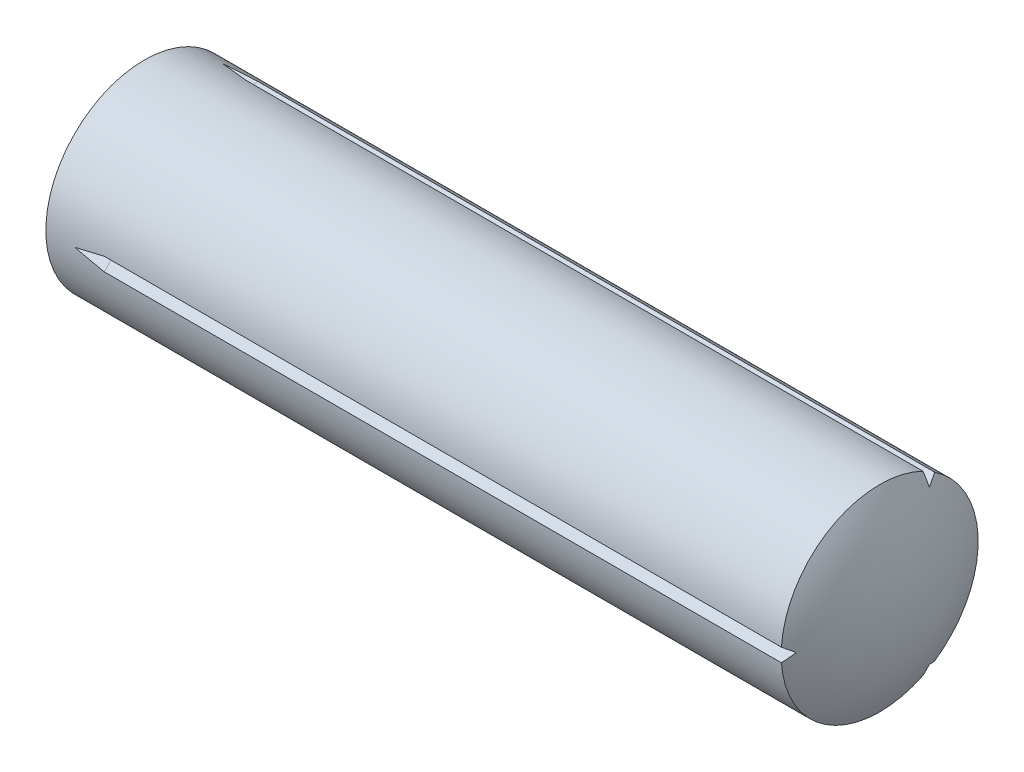
SolidWorks part; units mm, degrees
revolve "Base-Revolve" add sketch "Sketch1" angle 360 about L0
sketch "Sketch1" plane through (0, 0, 0) normal (0, 0, 1) x (1, 0, 0)
  line L0 (-117, 0) -> (21, 0) construction
  line L1 (-100, 0) -> (-100, 1.25)
  line L2 (-96.6819, 12.5) -> (-3.3494, 12.5)
  line L3 (-100, 0) -> (0, 0)
  arc A0 (-96.6819, 12.5) -> (-100, 1.25) centre (-75.0313, 0) ccw
  arc A1 (0, 0) -> (-3.3494, 12.5) centre (-25, 0) ccw
  dimension "D2" = 25
  dimension "D1" = 25
  dimension "Length" = 100
  dimension "D3" = 2.5
ref_plane "Plane1" through (0, 0, 0) normal (0, 0, 1) x (1, 0, 0)
ref_plane "Plane2" through (0, 0, 0) normal (0, 1, 0) x (1, 0, 0)
ref_plane "Plane3" through (0, 0, 0) normal (1, 0, 0) x (0, 0, -1)
sketch "Sketch2" plane through (0, 0, 0) normal (1, 0, 0) x (0, 0, -1)
  line L0 (0, 0) -> (-14, 0) construction
  line L1 (-11.25, 0) -> (-12.5, 0.8753)
  line L2 (-11.25, 0) -> (-12.5, -0.8753)
  line L3 (-12.5, -0.8753) -> (-12.5, 0.8753)
  circle A0 centre (0, 0) radius 11.25 construction
  circle A1 centre (0, 0) radius 12.5 construction
  dimension "D1" = 22.5
  dimension "D2" = 70
  dimension "D3" = 35
sketch "Sketch4" plane through (0, 0, 0) normal (0, 1, 0) x (1, 0, 0)
  line L0 (8, 0) -> (-110, 0) construction
  line L1 (-117, 0) -> (21, 0) construction
  line L2 (0, -11.25) -> (-89.5, -11.25)
  line L3 (-89.5, -11.25) -> (-93, -12.5)
  point P7 (-100, 0)
  dimension "D1" = 22.5
  dimension "D3" = 100
  dimension "D5" = 25
  dimension "D2" = 10.5
sweep "Cut-Sweep1" cut profiles "Sketch2" path "Sketch4"
pattern_circular "CirPattern1" count 3 over 360 about axis through (-117, 0, 0) along (1, 0, 0) of "Cut-Sweep1"
equation "\"D1@Sketch1\" = \"Diameter@Sketch1\""
equation "\"D2@Sketch1\" = \"Diameter@Sketch1\""
equation "\"D1@Sketch2\" = \"Diameter@Sketch1\" * .9"
equation "\"D3@Sketch2\" = \"D2@Sketch2\" / 2"
equation "\"D1@Sketch4\" = \"D1@Sketch2\""
equation "\"D3@Sketch4\" = \"Length@Sketch1\""
equation "\"D5@Sketch4\" = \"Diameter@Sketch1\""
equation "\"D2@Sketch4\" = \"Pilot@Sketch4\" * 1.5"
equation "\"D3@Sketch1\" = \"Diameter@Sketch1\" * .1"
